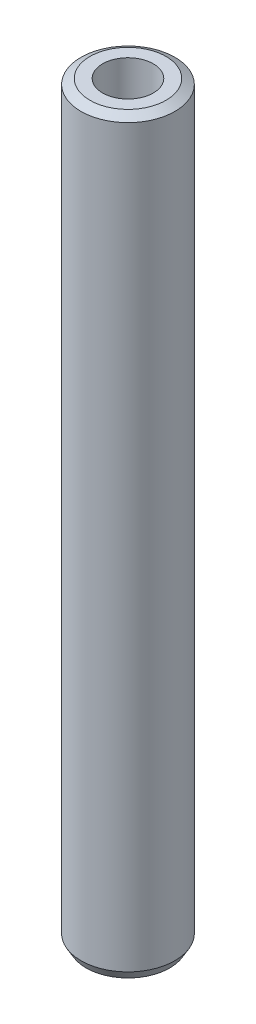
SolidWorks part; units mm, degrees
ref_plane "Front Plane" through (0, 0, 0) normal (0, 0, 1) x (1, 0, 0)
ref_plane "Top Plane" through (0, 0, 0) normal (0, 1, 0) x (1, 0, 0)
ref_plane "Right Plane" through (0, 0, 0) normal (1, 0, 0) x (0, 0, -1)
sketch "Sketch1" plane through (0, 0, 0) normal (0, 1, 0) x (1, 0, 0)
  circle A0 centre (0, 0) radius 32.5
  dimension "SHAFT_OD" = 65
extrude "Boss-Extrude1" add sketch "Sketch1" along normal blind 518.9077
sketch "Sketch2" plane through (0, 0, 0) normal (0, 1, 0) x (1, 0, 0)
  circle A0 centre (0, 0) radius 17.5398
  dimension "BORE_D" = 35.0796
extrude "Cut-Extrude1" cut sketch "Sketch2" along normal through all
chamfer "Chamfer1" distance 3.5685 angle 60 2 edges at (0, 518.9077, 32.5) (0, 0, 32.5) first distance on face at (0, 518.9077, 32.5) first distance on face at (0, 0, 17.5398)
